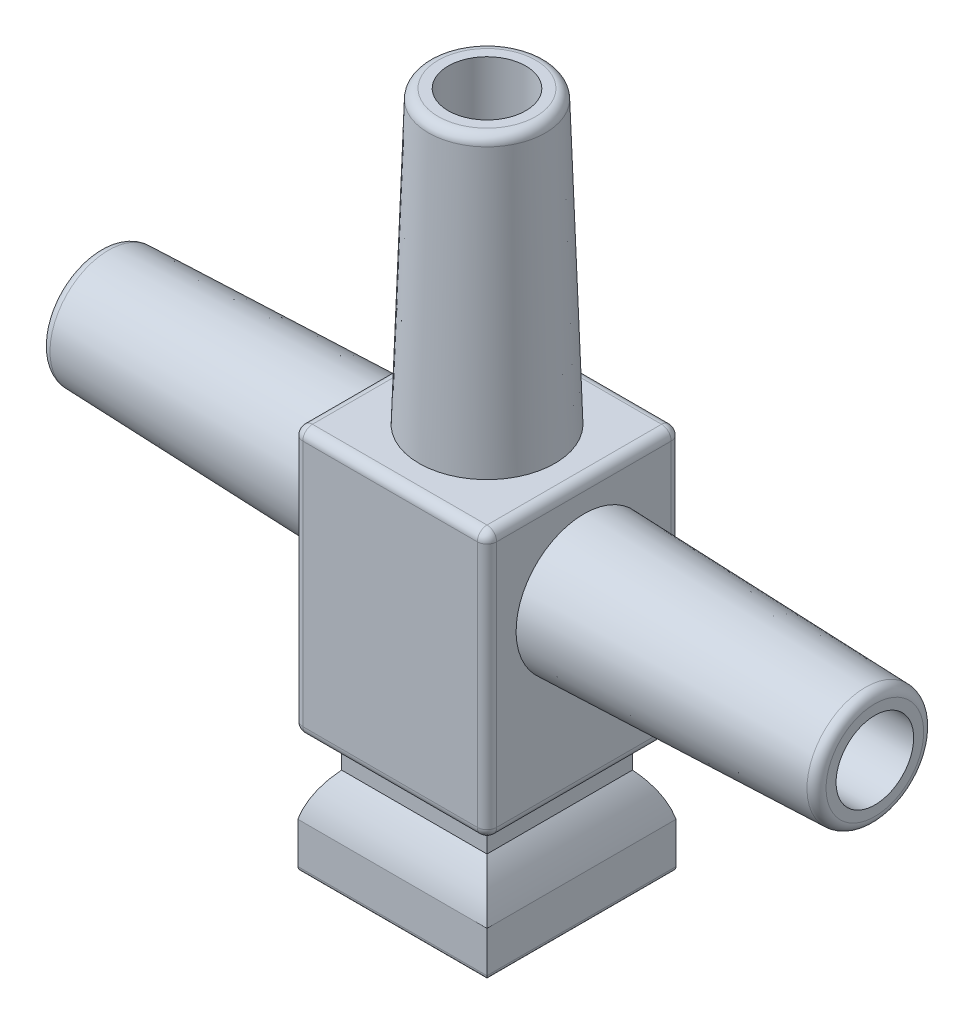
SolidWorks part; units mm, degrees
ref_plane "前视基准面" through (0, 0, 0) normal (0, 0, 1) x (1, 0, 0)
ref_plane "上视基准面" through (0, 0, 0) normal (0, 1, 0) x (1, 0, 0)
ref_plane "右视基准面" through (0, 0, 0) normal (1, 0, 0) x (0, 0, -1)
sketch "草图1" plane through (0, 0, 0) normal (0, 0, 1) x (1, 0, 0)
  line L0 (2, 2.75) -> (2, -2.75)
  line L1 (2, 2.75) -> (-2, 2.75)
  line L2 (2, -2.75) -> (-2, -2.75)
  line L3 (-2, 2.75) -> (-2, -2.75)
  line L4 (2, 2.75) -> (-2, -2.75) construction
  line L5 (2, -2.75) -> (-2, 2.75) construction
  point P1 (0, 0)
  dimension "D1" = 4
  dimension "D2" = 5.5
extrude "凸台-拉伸1" add sketch "草图1" along normal blind 2 and the other way blind 2
sketch "草图2" plane through (0, 0, 0) normal (0, 0, 1) x (1, 0, 0)
  line L0 (0, -2.75) -> (0, -4.75) construction
  line L1 (-2, -2.75) -> (2, -2.75) construction
  line L2 (0, -4.75) -> (0, -5.25) construction
  line L3 (-1.5, -2.75) -> (1.5, -2.75)
  line L4 (1.5, -2.75) -> (1.5, -3.4271)
  line L5 (-1.95, -5.25) -> (1.95, -5.25)
  line L6 (1.95, -5.25) -> (1.95, -4.3056)
  line L7 (-1.95, -5.25) -> (-1.95, -4.3056)
  line L8 (-1.5, -2.75) -> (-1.5, -3.4271)
  arc A0 (1.95, -4.3056) -> (1.5, -3.4271) centre (0, -4.75) ccw
  arc A1 (-1.95, -4.3056) -> (-1.5, -3.4271) centre (0, -4.75) cw
  dimension "D5" = 2
  dimension "D1" = 2
  dimension "D2" = 0.5
  dimension "D3" = 1.5
  dimension "D4" = 1.95
extrude "凸台-拉伸2" add sketch "草图2" along normal blind 2 and the other way blind 2
sketch "草图3" plane through (0, 0, 0) normal (1, 0, 0) x (0, 0, -1)
  line L0 (0, -2.75) -> (0, -4.75) construction
  line L1 (2, -2.75) -> (-2, -2.75) construction
  line L2 (0, -4.75) -> (0, -5.25) construction
  line L3 (2, -5.25) -> (-2, -5.25) construction
  line L4 (0, -2.75) -> (1.5, -2.75) construction
  line L5 (2, -2.75) -> (-2, -2.75) construction
  line L6 (1.5, -2.75) -> (1.5, -3.4271)
  line L7 (0, -5.25) -> (1.95, -5.25) construction
  line L8 (1.95, -5.25) -> (1.95, -4.3056)
  line L9 (1.5, -2.75) -> (2, -2.75)
  line L10 (2, -2.75) -> (2, -5.25)
  line L11 (2, -5.25) -> (1.95, -5.25)
  line L12 (-2, -5.25) -> (-1.95, -5.25)
  line L13 (-1.95, -5.25) -> (-1.95, -4.3056)
  line L14 (-2, -2.75) -> (-2, -5.25)
  line L15 (-1.5, -2.75) -> (-1.5, -3.4271)
  line L16 (-1.5, -2.75) -> (-2, -2.75)
  arc A0 (1.95, -4.3056) -> (1.5, -3.4271) centre (0, -4.75) ccw
  arc A1 (-1.95, -4.3056) -> (-1.5, -3.4271) centre (0, -4.75) cw
  dimension "D4" = 2
  dimension "D1" = 2
  dimension "D2" = 1.5
  dimension "D3" = 1.95
extrude "切除-拉伸1" cut sketch "草图3" against normal blind 2 and the other way blind 2
sketch "草图4" plane through (2, 0, 0) normal (1, 0, 0) x (0, 0, -1)
  line L0 (0, 2.75) -> (0, 0.75) construction
  line L1 (2, 2.75) -> (-2, 2.75) construction
  line L2 (0, 0.75) -> (0, -0.65) construction
  circle A0 centre (0, 0.75) radius 1.4
  dimension "D2" = 2.8
  dimension "D1" = 2
ref_plane "基准面1" through (8, 0, 0) normal (1, 0, 0) x (0, 0, -1)
sketch "草图5" plane through (8, 0, 0) normal (1, 0, 0) x (0, 0, -1)
  line L0 (0, 2.75) -> (0, 0.75) construction
  line L1 (0, 0.75) -> (0, -0.45) construction
  circle A0 centre (0, 0.75) radius 1.2
  dimension "D1" = 2.4
loft "放样2" add profiles "草图4", "草图5" connector at (2, -0.65, -0.0079) connector at (8, -0.4497, -0.0279)
mirror "镜向1" about plane through (0, 0, 0) normal (1, 0, 0) of "放样2"
sketch "草图6" plane through (0, 2.75, 0) normal (0, 1, 0) x (1, 0, 0)
  line L0 (0, 0) -> (0, 1.4) construction
  circle A0 centre (0, 0) radius 1.4
  dimension "D1" = 2.8
ref_plane "基准面2" through (0, 8.75, 0) normal (0, 1, 0) x (1, 0, 0)
sketch "草图7" plane through (0, 8.75, 0) normal (0, 1, 0) x (1, 0, 0)
  line L0 (0, 0) -> (0, 1.2) construction
  circle A0 centre (0, 0) radius 1.2
  dimension "D1" = 2.4
loft "放样3" add profiles "草图6", "草图7" connector at (-0.0009, 2.75, -1.4) connector at (-0.0008, 8.75, -1.2)
sketch "草图8" plane through (8, 0, 0) normal (1, 0, 0) x (0, 0, -1)
  circle A0 centre (0, 0.75) radius 0.8
  dimension "D1" = 1.6
extrude "切除-拉伸2" cut sketch "草图8" against normal through all
sketch "草图9" plane through (0, 8.75, 0) normal (0, 1, 0) x (1, 0, 0)
  circle A0 centre (0, 0) radius 0.8
  dimension "D1" = 1.6
extrude "切除-拉伸3" cut sketch "草图9" against normal blind 8
fillet "圆角1" radius 0.2 12 edges at (2, -2.75, 0) (-2, -2.75, 0) (2, 0, -2) (-2, 0, -2) (2, 0, 2) (-2, 0, 2) (0, 2.75, 2) (2, 2.75, 0) (0, 2.75, -2) (-2, 2.75, 0)
fillet "圆角2" radius 0.2 3 edges at (8, 1.95, 0) (0, 8.75, 1.2) (-8, 1.95, 0)
fillet "圆角3" radius 0.1 4 edges at (0, -5.25, 1.95) (1.95, -5.25, 0) (0, -5.25, -1.95) (-1.95, -5.25, 0)
